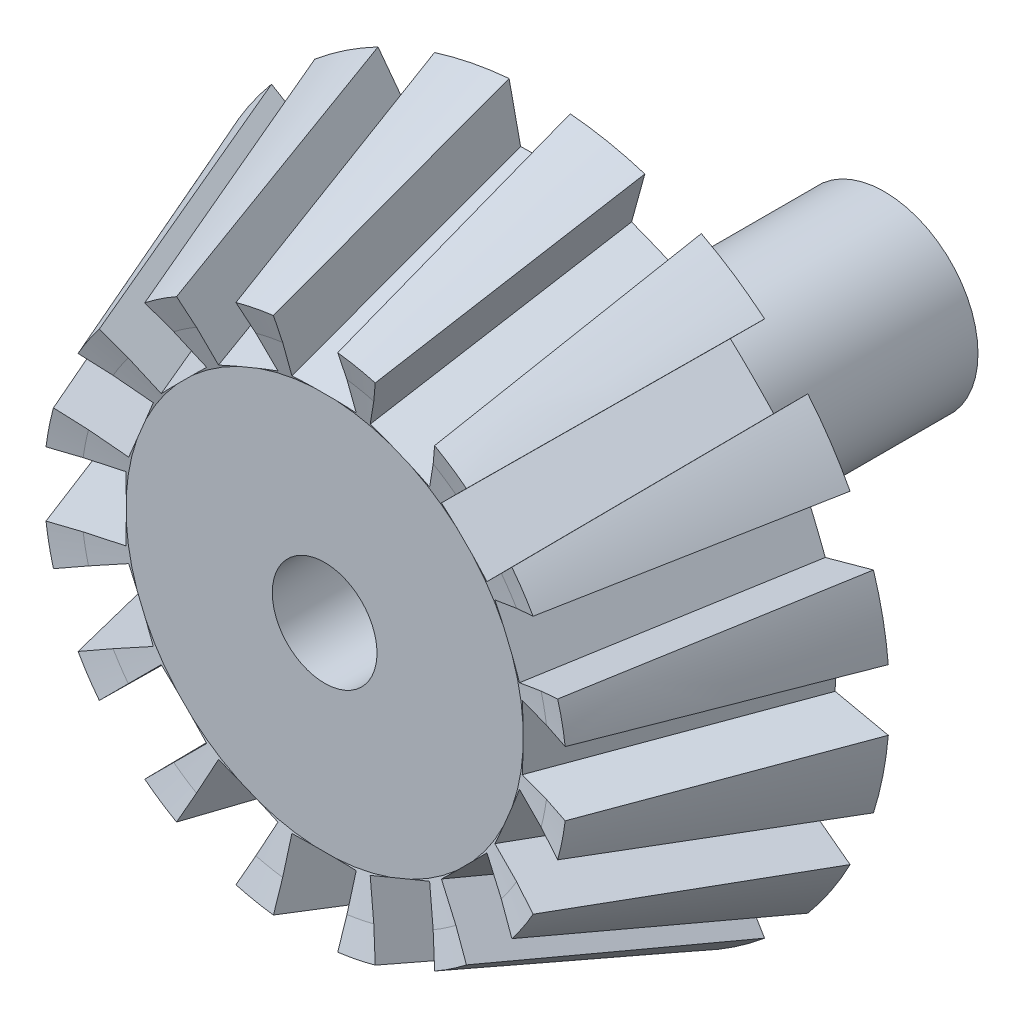
SolidWorks part; units mm, degrees
ref_plane "Front Plane" through (0, 0, 0) normal (0, 0, 1) x (1, 0, 0)
ref_plane "Top Plane" through (0, 0, 0) normal (0, 1, 0) x (1, 0, 0)
ref_plane "Right Plane" through (0, 0, 0) normal (1, 0, 0) x (0, 0, -1)
sketch "Sketch1" plane through (0, 0, 0) normal (1, 0, 0) x (0, 0, -1)
  line L0 (0, 0) -> (48.6951, 0) construction
  line L1 (0, 0) -> (36.3475, 10.1484) construction
  line L2 (0, 0) -> (36.0149, 12.0015) construction
  line L3 (0, 0) -> (35.7458, 13.5001) construction
  line L11 (35.7458, 13.5001) -> (26.7163, 10.0899)
  line L18 (27.4513, 0) -> (36.3475, 0)
  line L19 (35.7458, 13.5001) -> (36.3475, 10.1484)
  line L21 (26.7163, 10.0899) -> (27.0724, 9.0215)
  line L22 (27.0724, 9.0215) -> (27.4513, 7.6645)
  line L23 (27.4513, 7.6645) -> (27.4513, 0)
  line L26 (36.3475, 10.1484) -> (36.3475, 0)
  dimension "D1" = 15.6
  dimension "D2" = 18.43
  dimension "D3" = 20.69
  dimension "D4" = 9.652
  dimension "D6" = 12.0015
  dimension "D7" = 13.5001
revolve "Revolve1" add sketch "Sketch1" angle 360 about L0
ref_plane "Plane7" through (0, 0, 0) normal (0, 0.9355, 0.3533) x (1, 0, 0)
sketch "Sketch2" plane through (0, 0, 0) normal (0, 0.9355, 0.3533) x (1, 0, 0)
  line L0 (0, 40.6052) -> (0, 16.5207) construction
  line L1 (0, 0) -> (0, 45.5546) construction
  line L2 (1.2446, 27.7092) -> (1.1782, 38.3747)
  line L3 (0, 27.7092) -> (1.2446, 27.7092)
  line L5 (1.1782, 38.3747) -> (0, 38.3747)
  line L9 (-1.1782, 38.3747) -> (0, 38.3747)
  line L10 (0, 27.7092) -> (-1.2446, 27.7092)
  line L11 (-1.2446, 27.7092) -> (-1.1782, 38.3747)
  point P9 (0, 38.3747)
  dimension "D1" = 2.3564
  dimension "D2" = 2.4892
extrude "Cut-Extrude2" cut sketch "Sketch2" against normal blind 2.54 contours L5 L9 L11 L10 L3 L2
pattern_circular "CirPattern2" count 16 over 360 about axis through (0, 0, -27.0724) along (0, 0, 1) of "Revolve1", "Cut-Extrude2"
extrude "Cut-Extrude3" cut sketch "Sketch2<4>" against normal blind 2.54
sketch "Sketch2<4>" plane through (0, 0, 0) normal (0, 0.9355, 0.3533) x (1, 0, 0) same geometry as "Sketch2"
sketch "Sketch3" plane through (0, 0, -36.3475) normal (0, 0, -1) x (-1, 0, 0)
  circle A0 centre (0, 0) radius 3.6068
  circle A1 centre (0, 0) radius 2.0193
  dimension "D1" = 7.2136
  dimension "D2" = 4.0386
extrude "Boss-Extrude1" add sketch "Sketch3" along normal blind 12.7
sketch "Sketch4" plane through (0, 0, -36.3475) normal (0, 0, -1) x (-1, 0, 0)
  circle A0 centre (0, 0) radius 2.0193
  dimension "D1" = 4.0386
extrude "Cut-Extrude4" cut sketch "Sketch4" against normal through all both and the other way through all
